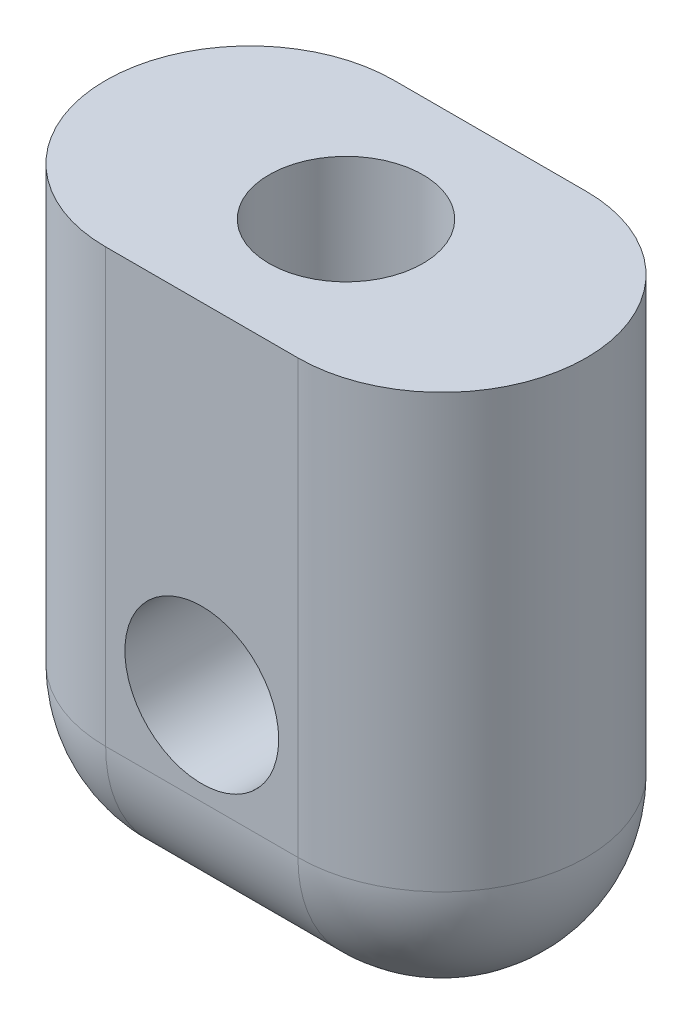
SolidWorks part; units mm, degrees
ref_plane "Front Plane" through (0, 0, 0) normal (0, 0, 1) x (1, 0, 0)
ref_plane "Top Plane" through (0, 0, 0) normal (0, 1, 0) x (1, 0, 0)
ref_plane "Right Plane" through (0, 0, 0) normal (1, 0, 0) x (0, 0, -1)
sketch "Sketch1" plane through (0, 0, 0) normal (0, 1, 0) x (1, 0, 0)
  line L0 (0, 0) -> (4, 0) construction
  line L1 (0, 3) -> (4, 3)
  line L2 (0, -3) -> (4, -3)
  arc A0 (0, 3) -> (0, -3) centre (0, 0) ccw
  arc A1 (4, -3) -> (4, 3) centre (4, 0) ccw
  point P3 (2, 0)
  dimension "D1" = 6
  dimension "D2" = 4
extrude "Boss-Extrude1" add sketch "Sketch1" along normal blind 12
fillet "Fillet3" radius 3 4 edges at (2, 0, -3) (2, 0, 3) (-3, 0, 0) (7, 0, 0)
sketch "Sketch2" plane through (0, 0, 3) normal (0, 0, 1) x (1, 0, 0)
  circle A0 centre (2, 4.926) radius 1.6
  point P2 (0, 0)
  point P3 (2, 4.926)
  point P4 (0, 0)
  dimension "D1" = 3.2
extrude "Cut-Extrude1" cut sketch "Sketch2" against normal blind 20 contours A0
sketch "Sketch4" plane through (0, 12, 0) normal (0, 1, 0) x (1, 0, 0)
  line L0 (0, -3) -> (4, 3) construction
  line L2 (0, -3) -> (4, -3)
  line L3 (4, 3) -> (0, 3)
  line L4 (0, -3) -> (4, -3)
  line L5 (4, 3) -> (0, 3)
  circle A0 centre (2, 0) radius 1.6
  arc A2 (0, 3) -> (0, -3) centre (0, 0) ccw
  arc A3 (4, -3) -> (4, 3) centre (4, 0) ccw
  arc A4 (0, 3) -> (0, -3) centre (0, 0) ccw
  arc A5 (4, -3) -> (4, 3) centre (4, 0) ccw
  dimension "D2" = 3.2
  dimension "D1" = 0
extrude "Cut-Extrude2" cut sketch "Sketch4" against normal blind 4 contours A0
